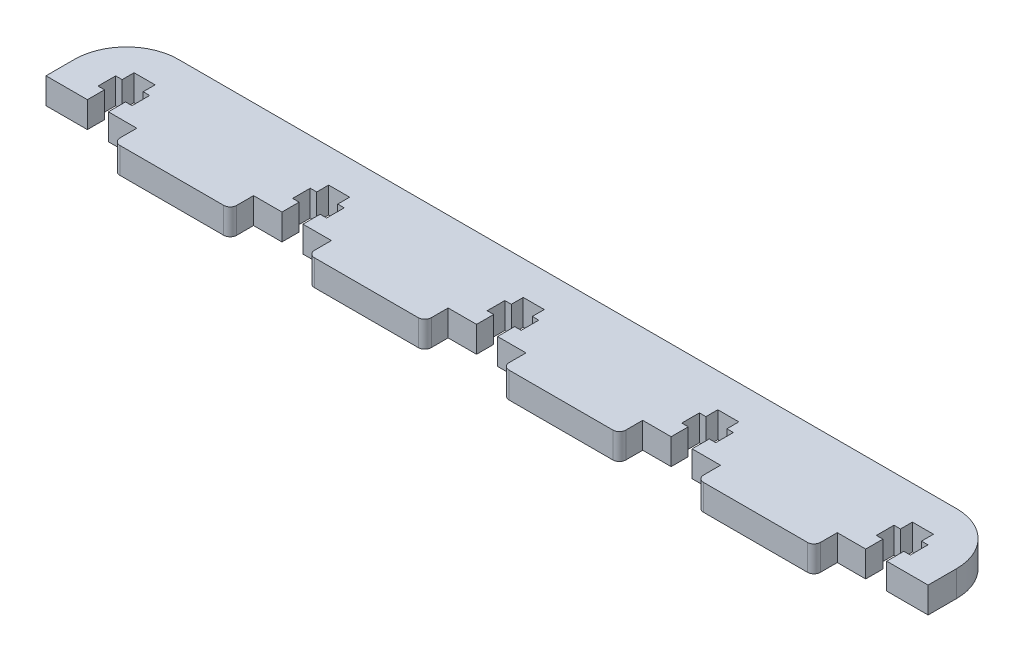
SolidWorks part; units mm, degrees
ref_plane "Front Plane" through (0, 0, 0) normal (0, 0, 1) x (1, 0, 0)
ref_plane "Top Plane" through (0, 0, 0) normal (0, 1, 0) x (1, 0, 0)
ref_plane "Right Plane" through (0, 0, 0) normal (1, 0, 0) x (0, 0, -1)
sketch "Sketch1" plane through (0, 0, 0) normal (0, 1, 0) x (1, 0, 0)
  line L1 (-170, 20) -> (170, 20)
  line L2 (-170, 20) -> (-170, -20)
  line L3 (-170, -20) -> (170, -20)
  line L4 (170, 20) -> (170, -20)
  line L5 (-170, 20) -> (170, -20) construction
  line L6 (-170, -20) -> (170, 20) construction
  point P0 (0, 0)
  dimension "D1" = 40
  dimension "D2" = 340
extrude "Boss-Extrude1" add sketch "Sketch1" along normal blind 10 contours L1 L4 L3 L2
sketch "Sketch2" plane through (0, 10, 0) normal (0, 1, 0) x (1, 0, 0)
  line L0 (0, -6.9) -> (0, -20) construction
  line L1 (-170, -20) -> (170, -20) construction
  line L3 (-4.05, 7) -> (4.05, 7)
  line L4 (-4.05, 7) -> (-4.05, -20)
  line L5 (-4.05, -20) -> (4.05, -20)
  line L6 (4.05, 7) -> (4.05, -20)
  line L7 (-4.05, 7) -> (4.05, -20) construction
  line L8 (-4.05, -20) -> (4.05, 7) construction
  line L9 (-6.55, 2.4) -> (6.55, 2.4)
  line L10 (-6.55, 2.4) -> (-6.55, -4.4)
  line L11 (-6.55, -4.4) -> (6.55, -4.4)
  line L12 (6.55, 2.4) -> (6.55, -4.4)
  line L13 (-6.55, 2.4) -> (6.55, -4.4) construction
  line L14 (-6.55, -4.4) -> (6.55, 2.4) construction
  line L15 (-15, -11) -> (15, -11)
  line L16 (-15, -11) -> (-15, -20)
  line L17 (-15, -20) -> (15, -20)
  line L18 (15, -11) -> (15, -20)
  line L19 (-15, -11) -> (15, -20) construction
  line L20 (-15, -20) -> (15, -11) construction
  point P4 (0, -6.5)
  point P9 (0, -1)
  point P14 (0, -15.5)
  line M12 (-170, -20) -> (170, -20)
  dimension "D1" = 27
  dimension "D2" = 8.1
  dimension "D3" = 6.8
  dimension "D4" = 13.1
  dimension "D5" = 19
  dimension "D6" = 30
  dimension "D7" = 9
extrude "Cut-Extrude1" cut sketch "Sketch2" against normal through all contours L18 L15 L6 M12 | L15 L4 L6 M12 | L15 L16 L4 M12 | L4 L15 L6 L11 | L4 L11 L6 L9 | L10 L11 L4 L9 | L4 L9 L6 L3 | L12 L9 L6 L11 region at (0, 10, -4.7) region at (0, 10, 1) region at (-5.3, 10, 1) region at (5.3, 10, 1) region at (0, 10, 7.7) region at (0, 10, 15.5) region at (-9.525, 10, 15.5) region at (9.525, 10, 15.5)
fillet "Fillet1" radius 2.5 2 edges at (15, 5, 20) (-15, 5, 20)
pattern_linear "LPattern1" count 3 spacing 75 along (1, 0, 0) count 3 spacing 75 along (-1, 0, 0) of "Cut-Extrude1", "Fillet1" pattern seed only yes
sketch "Sketch3" plane through (0, 10, 0) normal (0, 1, 0) x (1, 0, 0)
  line L1 (-165, -11) -> (-170, -11)
  line L2 (-165, -11) -> (-165, -20)
  line L3 (-165, -20) -> (-170, -20)
  line L4 (-170, -11) -> (-170, -20)
extrude "Cut-Extrude2" cut sketch "Sketch3" against normal through all
mirror "Mirror1" about plane through (0, 0, 0) normal (1, 0, 0) of "Cut-Extrude2"
fillet "Fillet2" radius 20 2 edges at (170, 5, -20) (-170, 5, -20)
